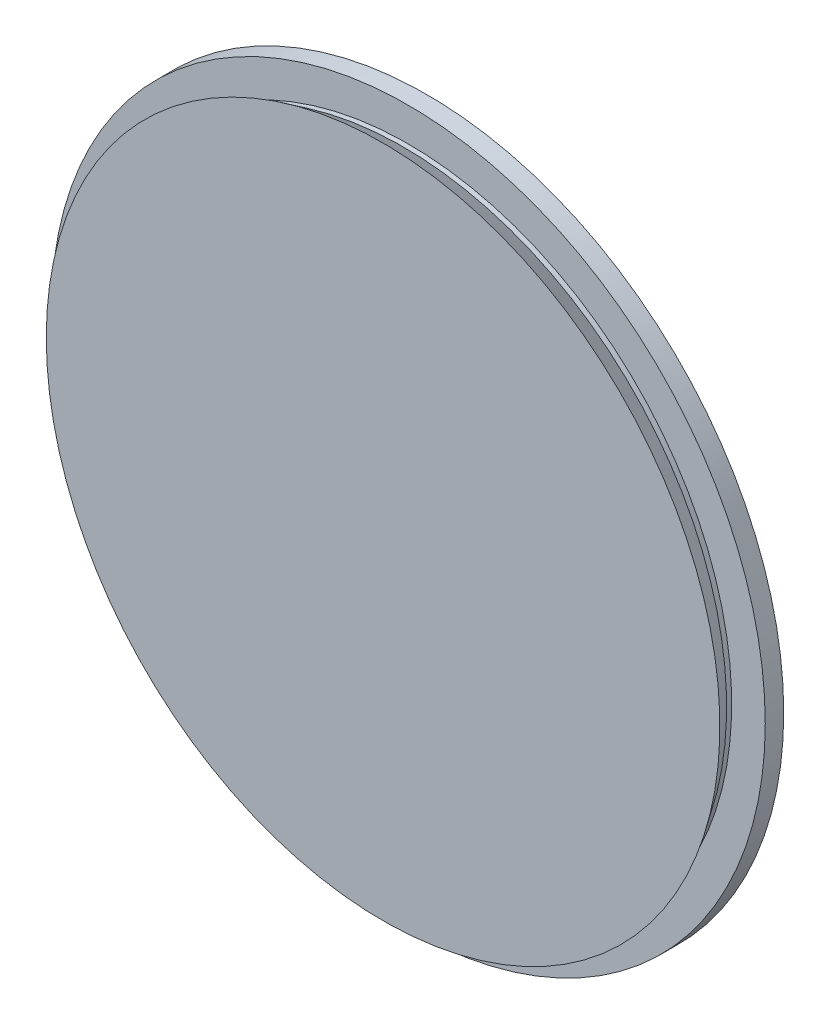
SolidWorks part; units mm, degrees
ref_plane "Front Plane" through (0, 0, 0) normal (0, 0, 1) x (1, 0, 0)
ref_plane "Top Plane" through (0, 0, 0) normal (0, 1, 0) x (1, 0, 0)
ref_plane "Right Plane" through (0, 0, 0) normal (1, 0, 0) x (0, 0, -1)
sketch "Sketch1" plane through (0, 0, 0) normal (0, 0, 1) x (1, 0, 0)
  circle A0 centre (0, 0) radius 19.25
  dimension "D1" = 38.5
extrude "Boss-Extrude1" add sketch "Sketch1" along normal blind 2.6
sketch "Sketch2" plane through (0, 0, 0) normal (0, 0, -1) x (-1, 0, 0)
  circle A0 centre (0, 0) radius 21.25
  circle A1 centre (0, 0) radius 19.25
  circle A2 centre (0, 0) radius 19.25
  dimension "D2" = 2
  dimension "D1" = 0
extrude "Boss-Extrude2" add sketch "Sketch2" against normal blind 1.1
sketch "Sketch3" plane through (0, 0, 0) normal (0, 1, 0) x (1, 0, 0)
  line L0 (-19.25, -1.4) -> (-20.05, -2.6)
  line L1 (-19.25, -1.1) -> (-19.25, -2.6) construction
  line L2 (-20.05, -2.6) -> (-19.25, -2.6)
  line L3 (-19.25, -2.6) -> (-19.25, -1.4)
  line L4 (-19.25, -2.6) -> (19.25, -2.6) construction
  line L5 (-19.25, -1.1) -> (-19.25, -2.6) construction
  point P7 (-19.25, -1.8)
  point P10 (-19.25, -3)
  dimension "D1" = 0.8
  dimension "D2" = 1.2
sketch "Sketch4" plane through (0, 0, 2.6) normal (0, 0, 1) x (1, 0, 0)
  circle A1 centre (0, 0) radius 19.25
  circle A2 centre (0, 0) radius 19.25
  dimension "D1" = 0
sweep "Sweep1" add profiles "Sketch3" path "Sketch4"
